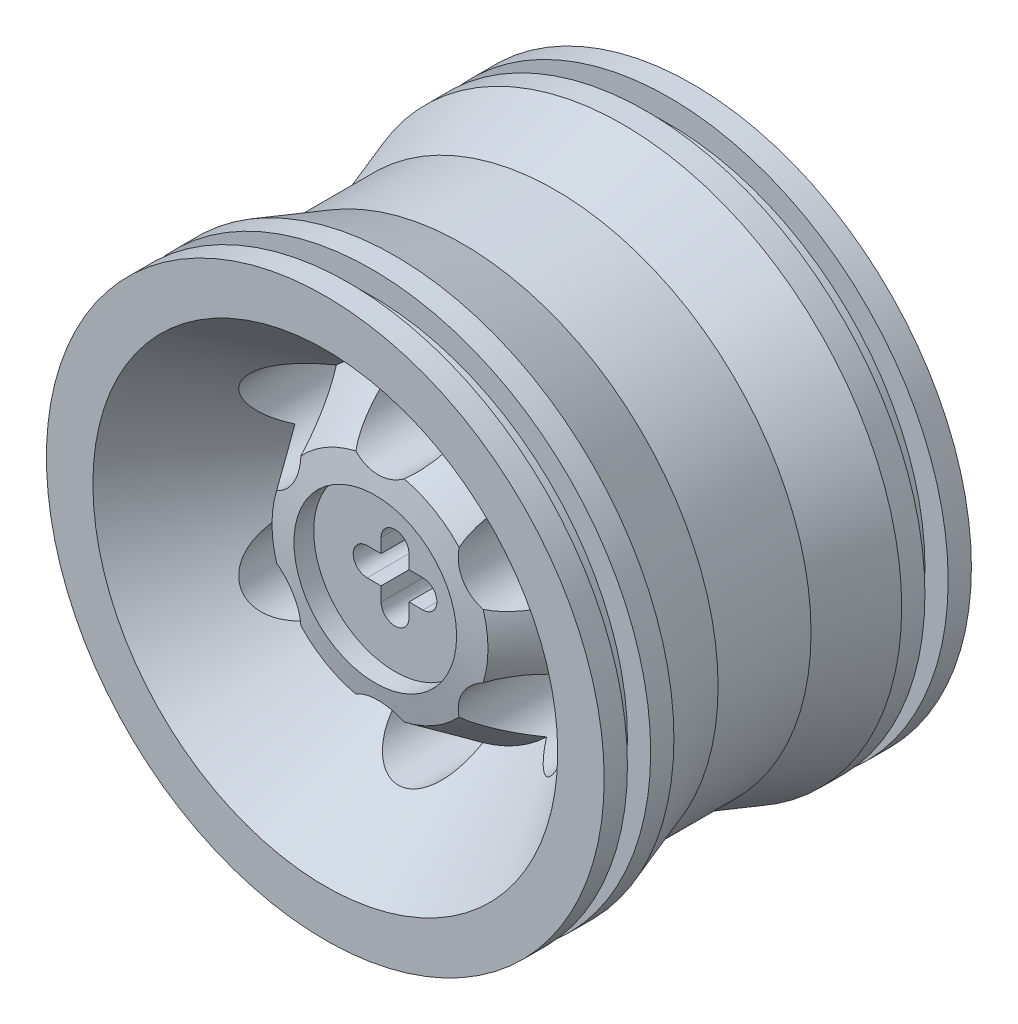
SolidWorks part; units mm, degrees
material "PVC Rigid"
ref_plane "Front Plane" through (0, 0, 0) normal (0, 0, 1) x (1, 0, 0)
ref_plane "Top Plane" through (0, 0, 0) normal (0, 1, 0) x (1, 0, 0)
ref_plane "Right Plane" through (0, 0, 0) normal (1, 0, 0) x (0, 0, -1)
sketch "Sketch1" plane through (0, 0, 0) normal (0, 1, 0) x (1, 0, 0)
  line L0 (-7.62, 3.81) -> (0, 3.81)
  line L1 (-7.62, -3.81) -> (0, -3.81)
  circle A0 centre (0, 0) radius 2.286 construction
  arc A1 (0, -3.81) -> (0, 3.81) centre (0, 0) ccw
  arc A2 (-7.62, 3.81) -> (-7.62, -3.81) centre (-7.62, 0) ccw
  dimension "D1" = 7.62
  dimension "D2" = 4.572
  dimension "D3" = 7.62
extrude "Extrude1" add sketch "Sketch1" along normal blind 3.81
ref_plane "Plane1" through (0, 0, 3.81) normal (0, 0, 1) x (1, 0, 0)
sketch "Sketch4" plane through (0, 0, 3.81) normal (0, 0, 1) x (1, 0, 0)
  line L0 (0, 0) -> (0, 3.81)
  line L2 (0, 3.81) -> (7.62, 3.81)
  line L4 (7.62, 0) -> (0, 0)
  line L5 (7.62, 0) -> (11.43, 0)
  arc A0 (11.43, 0) -> (7.62, 3.81) centre (7.62, 0) ccw
  dimension "D2" = 3.81
  dimension "D1" = 7.62
extrude "Extrude2" add sketch "Sketch4" against normal blind 0.508
sketch "Sketch6" plane through (0, 0, 3.81) normal (0, 0, 1) x (1, 0, 0)
  line L0 (6.858, 2.032) -> (6.858, 1.016)
  line L1 (6.604, 0.762) -> (5.588, 0.762)
  line L2 (5.334, 0.508) -> (5.334, -0.508)
  line L3 (5.588, -0.762) -> (6.604, -0.762)
  line L4 (6.858, -1.016) -> (6.858, -2.032)
  line L5 (7.112, -2.286) -> (8.128, -2.286)
  line L6 (8.382, -2.032) -> (8.382, -1.016)
  line L7 (8.636, -0.762) -> (9.652, -0.762)
  line L8 (9.906, -0.508) -> (9.906, 0.508)
  line L9 (9.652, 0.762) -> (8.636, 0.762)
  line L10 (8.382, 1.016) -> (8.382, 2.032)
  line L11 (8.128, 2.286) -> (7.112, 2.286)
  line L12 (7.62, 1.454) -> (7.62, -1.454) construction
  line L13 (3.4212, 0) -> (11.8188, 0) construction
  arc A0 (6.858, 1.016) -> (6.604, 0.762) centre (6.604, 1.016) cw
  arc A1 (6.858, 2.032) -> (7.112, 2.286) centre (7.112, 2.032) cw
  arc A2 (8.128, 2.286) -> (8.382, 2.032) centre (8.128, 2.032) cw
  arc A3 (8.382, 1.016) -> (8.636, 0.762) centre (8.636, 1.016) ccw
  arc A4 (9.652, 0.762) -> (9.906, 0.508) centre (9.652, 0.508) cw
  arc A5 (9.652, -0.762) -> (9.906, -0.508) centre (9.652, -0.508) ccw
  arc A6 (8.636, -0.762) -> (8.382, -1.016) centre (8.636, -1.016) ccw
  arc A7 (8.382, -2.032) -> (8.128, -2.286) centre (8.128, -2.032) cw
  arc A8 (7.112, -2.286) -> (6.858, -2.032) centre (7.112, -2.032) cw
  arc A9 (6.604, -0.762) -> (6.858, -1.016) centre (6.604, -1.016) cw
  arc A10 (5.588, -0.762) -> (5.334, -0.508) centre (5.588, -0.508) cw
  arc A11 (5.334, 0.508) -> (5.588, 0.762) centre (5.588, 0.508) cw
  arc A13 (11.43, 0) -> (7.62, 3.81) centre (7.62, 0) ccw construction
  point P40 (7.62, 0)
  dimension "D6" = 0.254
  dimension "D1" = 4.572
  dimension "D2" = 4.572
  dimension "D3" = 1.524
  dimension "D4" = 1.524
  dimension "D5" = 1.524
extrude "Cut-Extrude2" cut sketch "Sketch6" against normal through all
sketch "Sketch8" plane through (0, 0, 3.302) normal (0, 0, -1) x (-1, 0, 0)
  line L0 (-10.795, 0) -> (-10.414, 0)
  line L1 (-4.826, 0) -> (-4.445, 0)
  line L2 (-7.62, 0) -> (-7.62, 5.3462) construction
  line L4 (-8.001, 2.7679) -> (-8.001, 3.1521)
  line L6 (-7.239, 2.7679) -> (-7.239, 3.1521)
  arc A0 (-4.445, 0) -> (-7.239, 3.1521) centre (-7.62, 0) ccw
  arc A1 (-4.826, 0) -> (-7.239, 2.7679) centre (-7.62, 0) ccw
  arc A2 (-8.001, 3.1521) -> (-10.795, 0) centre (-7.62, 0) ccw
  arc A3 (-8.001, 2.7679) -> (-10.414, 0) centre (-7.62, 0) ccw
  dimension "D1" = 5.588
  dimension "D2" = 6.35
  dimension "D3" = 0.762
extrude "Extrude3" add sketch "Sketch8" along normal blind 3.302
sketch "Sketch9" plane through (0, 0, 0) normal (0, 0, -1) x (-1, 0, 0)
  line L0 (-4.826, 0) -> (-4.445, 0) construction
  line L2 (-4.6355, 0) -> (-1.0818, 0)
  line L3 (-4.6355, 0) -> (-4.6355, 0.1905)
  line L4 (-4.6355, 0.1905) -> (-1.0818, 0.1905)
  line L5 (-1.0818, 0) -> (-1.0818, 0.1905)
  dimension "D1" = 0.1905
extrude "Extrude4" add sketch "Sketch9" against normal through all
mirror "Mirror5" about plane through (7.62, 0, 0) normal (0, 0, -1) of "Cut-Extrude2", "Extrude3", "Extrude2", "Extrude4"
sketch "Sketch11" plane through (0, 3.81, 0) normal (0, 1, 0) x (1, 0, 0)
  circle A0 centre (0, 0) radius 2.286
  circle A1 centre (-7.62, 0) radius 2.286
  arc A2 (-7.62, 3.81) -> (-7.62, -3.81) centre (-7.62, 0) ccw construction
  dimension "D1" = 4.572
extrude "Cut-Extrude3" cut sketch "Sketch11" against normal through all
sketch "Sketch12" plane through (0, 3.81, 0) normal (0, 1, 0) x (1, 0, 0)
  circle A0 centre (0, 0) radius 3.175
  circle A1 centre (-7.62, 0) radius 3.175
  dimension "D1" = 6.35
extrude "Cut-Extrude4" cut sketch "Sketch12" against normal blind 0.508
mirror "Mirror6" about plane through (-7.62, 0, 0) normal (0, 1, 0) of bodies 108
sketch "Sketch13" plane through (0, 0, 3.81) normal (0, 0, 1) x (1, 0, 0)
  circle A0 centre (7.62, 0) radius 3.81
extrude "Cut-Extrude5" cut sketch "Sketch13" against normal through all flip side to cut
sketch "Sketch15" plane through (0, 0, -3.302) normal (0, 0, 1) x (1, 0, 0)
  line L1 (4.486, 2.1667) -> (5.2992, 2.1667)
  line L3 (4.492, -2.1753) -> (5.3073, -2.1753)
  arc A0 (4.486, 2.1667) -> (4.492, -2.1753) centre (7.62, 0) ccw
  arc A1 (5.2992, 2.1667) -> (5.3073, -2.1753) centre (7.62, 0) ccw
extrude "Cut-Extrude7" cut sketch "Sketch15" along normal up to surface (6.604 mm away) up to face at (7.62, 0, 3.302)
scale "Scale1" scale about origin uniform scaling no x scale factor 1 y scale factor 1 z scale factor 2.633333
sketch "Sketch18" plane through (0, 0, -10.033) normal (0, 0, -1) x (-1, 0, 0)
  line L0 (-7.62, 2.286) -> (-7.62, -2.286) construction
  line L1 (-8.128, 2.286) -> (-7.112, 2.286) construction
  line L2 (-8.128, -2.286) -> (-7.112, -2.286) construction
  point P6 (-7.62, 0)
sketch "Sketch17" plane through (0, 0, 0) normal (0, 1, 0) x (1, 0, 0)
  line L0 (10.414, 10.033) -> (10.414, -10.033)
  line L1 (10.414, -10.033) -> (22.86, -10.033)
  line L2 (22.86, 10.033) -> (22.86, 8.763)
  line L3 (22.86, 8.763) -> (21.59, 8.763)
  line L4 (22.86, 10.033) -> (10.414, 10.033)
  line L5 (0, 0) -> (22.5835, 0) construction
  line L6 (21.59, 8.763) -> (21.59, 7.493)
  line L7 (21.59, 7.493) -> (22.86, 7.493)
  line L8 (22.86, 7.493) -> (22.86, 6.223)
  line L9 (22.86, 6.223) -> (21.59, 2.54)
  line L10 (21.59, 2.54) -> (21.59, -2.54)
  line L11 (22.86, -6.223) -> (21.59, -2.54)
  line L12 (22.86, -6.223) -> (22.86, -7.493)
  line L13 (22.86, -7.493) -> (21.59, -7.493)
  line L14 (21.59, -7.493) -> (21.59, -8.763)
  line L15 (21.59, -8.763) -> (22.86, -8.763)
  line L16 (22.86, -8.763) -> (22.86, -10.033)
  line L17 (7.62, 0) -> (7.62, 13.8284) construction
  dimension "D1" = 20.066
  dimension "D2" = 1.27
  dimension "D3" = 1.27
  dimension "D4" = 1.27
  dimension "D5" = 5.08
  dimension "D6" = 1.27
  dimension "D7" = 15.24
  dimension "D8" = 12.446
revolve "Revolve1" add sketch "Sketch17" angle 360 about L17
sketch "Sketch20" plane through (0, 0, 0) normal (0, 0, 1) x (1, 0, 0)
  line L0 (7.62, 0) -> (7.62, 15.2143) construction
  circle A0 centre (7.62, 7.62) radius 2.286
  circle A1 centre (7.62, 0) radius 7.62 construction
  circle A2 centre (14.2191, 3.81) radius 2.286
  circle A3 centre (14.2191, -3.81) radius 2.286
  circle A4 centre (7.62, -7.62) radius 2.286
  circle A5 centre (1.0209, -3.81) radius 2.286
  circle A6 centre (1.0209, 3.81) radius 2.286
  dimension "D1" = 15.24
  dimension "D2" = 4.572
extrude "Extrude6" cut sketch "Sketch20" against normal through all and the other way through all
sketch "Sketch21" plane through (0, 0, 10.033) normal (0, 0, 1) x (1, 0, 0)
  circle A0 centre (7.62, 0) radius 12.7
  circle A2 centre (7.62, 0) radius 3.81
  dimension "D1" = 7.62
  dimension "D2" = 25.4
extrude "Extrude7" cut sketch "Sketch21" against normal blind 10.16 draft 35
mirror "Mirror7" about plane through (0, 0, 0) normal (0, 0, 1) of "Extrude7"
sketch "Sketch22" [suppressed] plane through (0, 0, 0) normal (0, 1, 0) x (1, 0, 0)
  line L0 (22.86, -8.763) -> (22.86, -10.033) construction
  line L1 (21.59, -8.763) -> (22.86, -8.763) construction
  line L2 (21.59, -7.493) -> (21.59, -8.763) construction
  line L3 (22.86, -7.493) -> (21.59, -7.493) construction
  line L4 (22.86, -6.223) -> (22.86, -7.493) construction
  line L5 (22.86, -6.223) -> (21.59, -2.54) construction
  line L6 (21.59, 2.54) -> (21.59, -2.54) construction
  line L7 (22.86, 6.223) -> (21.59, 2.54) construction
  line L8 (22.86, 7.493) -> (22.86, 6.223) construction
  line L9 (21.59, 7.493) -> (22.86, 7.493) construction
  line L10 (21.59, 8.763) -> (21.59, 7.493) construction
  line L11 (22.86, 8.763) -> (21.59, 8.763) construction
  line L12 (22.86, 10.033) -> (22.86, 8.763) construction
  line L13 (22.86, -8.763) -> (22.86, -10.033)
  line L14 (21.59, -8.763) -> (22.86, -8.763)
  line L15 (21.59, -7.493) -> (21.59, -8.763)
  line L16 (22.86, -7.493) -> (21.59, -7.493)
  line L17 (22.86, -6.223) -> (22.86, -7.493)
  line L18 (22.86, -6.223) -> (21.59, -2.54)
  line L19 (21.59, 2.54) -> (21.59, -2.54)
  line L20 (22.86, 6.223) -> (21.59, 2.54)
  line L21 (22.86, 7.493) -> (22.86, 6.223)
  line L22 (21.59, 7.493) -> (22.86, 7.493)
  line L23 (21.59, 8.763) -> (21.59, 7.493)
  line L24 (22.86, 8.763) -> (21.59, 8.763)
  line L25 (22.86, 10.033) -> (22.86, 8.763)
  line L26 (0, 0) -> (22.5835, 0) construction
  line L27 (0, 0) -> (22.5835, 0) construction
  line L28 (22.86, 10.033) -> (25.527, 12.7)
  line L29 (25.527, 12.7) -> (28.067, 12.7)
  line L30 (28.067, 12.7) -> (31.1785, 9.5885)
  line L31 (31.1785, 9.5885) -> (31.1785, 8.1915)
  line L32 (31.1785, 8.1915) -> (32.4485, 8.1915)
  line L33 (32.4485, 8.1915) -> (35.56, 5.08)
  line L34 (35.56, 5.08) -> (35.56, -5.08)
  line L35 (35.56, -5.08) -> (32.4485, -8.1915)
  line L36 (32.4485, -8.1915) -> (31.1785, -8.1915)
  line L37 (31.1785, -8.1915) -> (31.1785, -9.5885)
  line L38 (31.1785, -9.5885) -> (28.067, -12.7)
  line L39 (28.067, -12.7) -> (25.527, -12.7)
  line L40 (25.527, -12.7) -> (22.86, -10.033)
  line L41 (7.62, 0) -> (7.62, 13.8284) construction
  dimension "D1" = 27.94
  dimension "D2" = 25.4
  dimension "D3" = 135
  dimension "D4" = 10.16
  dimension "D5" = 1.27
  dimension "D6" = 2.54
sketch "Sketch23" plane through (0, 0, 10.033) normal (0, 0, 1) x (1, 0, 0)
  circle A1 centre (7.62, 0) radius 4.445
  dimension "D1" = 8.89
extrude "Extrude8" cut sketch "Sketch23" against normal blind 3.81
sketch "Sketch24" plane through (0, 0, -10.033) normal (0, 0, -1) x (-1, 0, 0)
  line L0 (-7.62, 2.286) -> (-7.62, -2.286) construction
  circle A0 centre (-7.62, 0) radius 4.445
  circle A1 centre (-7.62, 0) radius 4.445 construction
extrude "Extrude9" cut sketch "Sketch24" against normal blind 3.81
sketch "Sketch25" plane through (0, 0, 6.223) normal (0, 0, 1) x (1, 0, 0)
  line L12 (6.096, 0) -> (9.144, 0) construction
  line L13 (6.096, 0.762) -> (9.144, 0.762)
  line L14 (6.096, -0.762) -> (9.144, -0.762)
  line L15 (7.62, 1.524) -> (7.62, -1.524) construction
  line L16 (8.382, 1.524) -> (8.382, -1.524)
  line L17 (6.858, 1.524) -> (6.858, -1.524)
  circle A1 centre (7.62, 0) radius 4.445
  circle A2 centre (7.62, 0) radius 4.445
  arc A14 (6.096, 0.762) -> (6.096, -0.762) centre (6.096, 0) ccw
  arc A15 (9.144, -0.762) -> (9.144, 0.762) centre (9.144, 0) ccw
  arc A16 (8.382, 1.524) -> (6.858, 1.524) centre (7.62, 1.524) ccw
  arc A17 (6.858, -1.524) -> (8.382, -1.524) centre (7.62, -1.524) ccw
  point P5 (7.62, 0)
  point P12 (7.62, 0)
  circle M2 centre (7.62, 0) radius 4.445
  circle M3 centre (7.62, 0) radius 2.794
  dimension "D2" = 1.524
  dimension "D3" = 1.524
  dimension "D1" = 0
extrude "Extrude10" add sketch "Sketch25" against normal blind 3.81 contours A17 L17 L14 A14 L13 A16 L16 A15 M3 | M2 M3 region at (3.3007, 0, 6.223) region at (4.905, 0, 6.223)
sketch "Sketch26" plane through (0, 0, -6.223) normal (0, 0, -1) x (-1, 0, 0)
  line L12 (-9.144, 0) -> (-6.096, 0) construction
  line L13 (-9.144, 0.762) -> (-6.096, 0.762)
  line L14 (-9.144, -0.762) -> (-6.096, -0.762)
  line L15 (-7.62, 1.524) -> (-7.62, -1.524) construction
  line L16 (-6.858, 1.524) -> (-6.858, -1.524)
  line L17 (-8.382, 1.524) -> (-8.382, -1.524)
  circle A1 centre (-7.62, 0) radius 4.445
  circle A2 centre (-7.62, 0) radius 4.445
  arc A14 (-9.144, 0.762) -> (-9.144, -0.762) centre (-9.144, 0) ccw
  arc A15 (-6.096, -0.762) -> (-6.096, 0.762) centre (-6.096, 0) ccw
  arc A16 (-6.858, 1.524) -> (-8.382, 1.524) centre (-7.62, 1.524) ccw
  arc A17 (-8.382, -1.524) -> (-6.858, -1.524) centre (-7.62, -1.524) ccw
  point P5 (-7.62, 0)
  point P12 (-7.62, 0)
  circle M2 centre (-7.62, 0) radius 4.445
  circle M3 centre (-7.62, 0) radius 2.794
  dimension "D2" = 1.524
  dimension "D3" = 1.524
  dimension "D1" = 0
extrude "Extrude11" add sketch "Sketch26" against normal blind 3.81 contours M2 M3 | A17 L17 L14 A14 L13 A16 L16 A15 M3 region at (11.9393, 0, -6.223) region at (10.335, 0, -6.223)
chamfer "Chamfer1" distance 2.54 angle 45 2 edges at (12.065, 0, -9.1261) (3.175, 0, 9.1261) first distance on face at (3.175, 0, -6.223) first distance on face at (3.175, 0, 9.1261)
